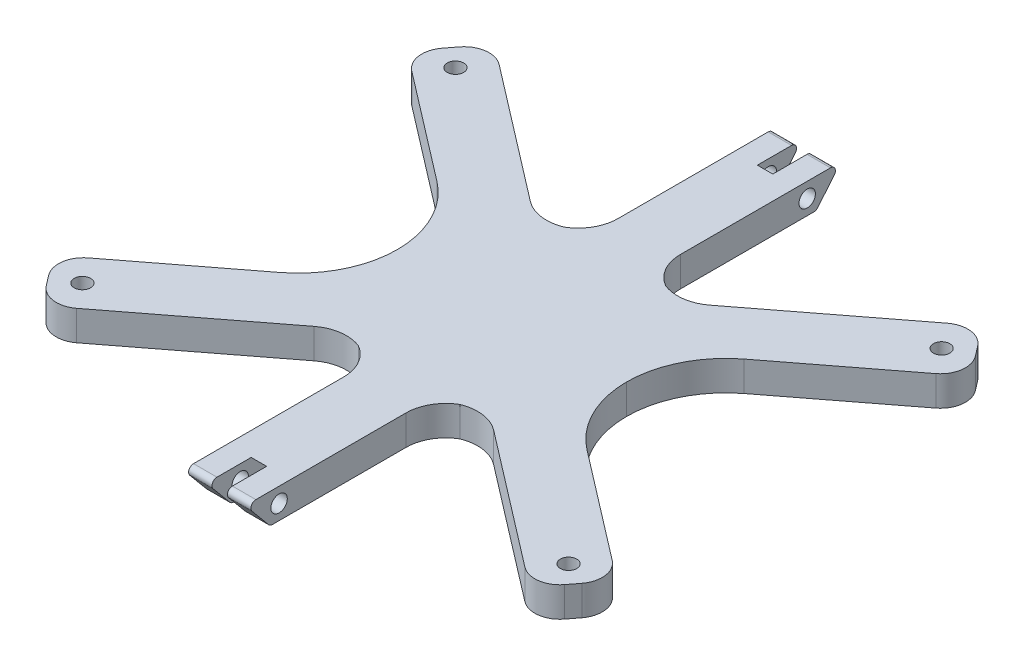
SolidWorks part; units mm, degrees
ref_plane "Front Plane" through (0, 0, 0) normal (0, 0, 1) x (1, 0, 0)
ref_plane "Top Plane" through (0, 0, 0) normal (0, 1, 0) x (1, 0, 0)
ref_plane "Right Plane" through (0, 0, 0) normal (1, 0, 0) x (0, 0, -1)
sketch "Sketch1" plane through (0, 0, 0) normal (0, 1, 0) x (1, 0, 0)
  circle A0 centre (0, 0) radius 23
  dimension "D1" = 46
extrude "Boss-Extrude1" add sketch "Sketch1" along normal mid plane 6
sketch "Sketch2" plane through (0, 0, 0) normal (0, 1, 0) x (1, 0, 0)
  line L0 (-21.3653, 8.5162) -> (-56.5628, 35.5242)
  line L1 (0.2695, -0.2068) -> (-63.7589, 48.924) construction
  line L2 (-48.9532, 45.4411) -> (-13.7557, 18.4331)
  line L3 (0, 37.6664) -> (0, -25.0328) construction
  line L4 (-48.9532, 45.4411) -> (-56.5628, 35.5242)
  circle A0 centre (0, 0) radius 23 construction
  arc A1 (-13.7557, 18.4331) -> (-21.3653, 8.5162) centre (0, 0) ccw
  point P9 (-52.758, 40.4826)
  dimension "D1" = 66.5
  dimension "D2" = 52.5
  dimension "D3" = 12.5
extrude "Boss-Extrude2" add sketch "Sketch2" along normal up to surface and the other way up to surface up to face at (0, 3, 23) other way up to face at (0, -3, 23)
mirror "Mirror1" about plane through (0, 0, 0) normal (1, 0, 0) of "Boss-Extrude2"
mirror "Mirror2" about plane through (0, 0, 0) normal (0, 0, 1) of "Mirror1", "Boss-Extrude2"
sketch "Sketch4" plane through (0, 3, 0) normal (0, 1, 0) x (1, 0, 0)
  line L0 (0, 65.599) -> (0, -44.8835) construction
  line L2 (-6.25, 59.8) -> (6.25, 59.8)
  line L4 (-6.25, 59.8) -> (-6.25, 22.1345)
  line L5 (6.25, 59.8) -> (6.25, 22.1345)
  arc A2 (13.7557, 18.4331) -> (-13.7557, 18.4331) centre (0, 0) ccw construction
  arc A3 (6.25, 22.1345) -> (-6.25, 22.1345) centre (0, 0) ccw
  point P8 (0, 59.8)
  dimension "D1" = 12.5
  dimension "D2" = 59.8
extrude "Boss-Extrude4" add sketch "Sketch4" against normal up to surface (6 mm away) up to face at (0, -3, 0)
mirror "Mirror6" about plane through (0, 0, 0) normal (0, 0, 1) of "Boss-Extrude4"
fillet "Fillet4" radius 8 8 edges at (-13.7557, 0, 18.4331) (-6.25, 0, 22.1345) (6.25, 0, 22.1345) (13.7557, 0, 18.4331) (13.7557, 0, -18.4331) (6.25, 0, -22.1345) (-6.25, 0, -22.1345) (-13.7557, 0, -18.4331)
fillet "Fillet5" radius 20 4 edges at (-21.3653, 0, 8.5162) (-21.3653, 0, -8.5162) (21.3653, 0, 8.5162) (21.3653, 0, -8.5162)
sketch "Sketch3" plane through (0, 3, 0) normal (0, 1, 0) x (1, 0, 0)
  circle A0 centre (-48.7912, 37.4388) radius 1.65
  dimension "D1" = 3.3
  dimension "D2" = 61.5
extrude "Cut-Extrude1" cut sketch "Sketch3" against normal through all
mirror "Mirror3" about plane through (0, 0, 0) normal (1, 0, 0) of "Cut-Extrude1"
mirror "Mirror4" about plane through (0, 0, 0) normal (0, 0, 1) of "Mirror3", "Cut-Extrude1"
sketch "Sketch13" plane through (-6.25, 0, 0) normal (-1, 0, 0) x (0, 0, 1)
  line L0 (-59.8, -3) -> (-59.8, 3) construction
  circle A0 centre (-53, 0) radius 1.65
  point P6 (-59.8, 0)
  dimension "D2" = 3.3
  dimension "D1" = 53
extrude "Cut-Extrude9" cut sketch "Sketch13" against normal blind 14
sketch "Sketch12" plane through (-6.25, 0, 0) normal (-1, 0, 0) x (0, 0, 1)
  line L0 (-59.8, 3) -> (-54.8, -3)
  line L2 (-54.8, -3) -> (-59.8, -3)
  line L3 (-59.8, -3) -> (-59.8, 3)
  line L4 (-27.5307, -3) -> (-59.8, -3) construction
  dimension "D1" = 5
extrude "Cut-Extrude8" cut sketch "Sketch12" against normal up to surface (12.5 mm away) up to face at (6.25, 0, -54.65)
sketch "Sketch14" plane through (0, 3, 0) normal (0, 1, 0) x (1, 0, 0)
  line L0 (-1.55, 59.8) -> (1.55, 59.8)
  line L1 (6.25, 59.8) -> (-6.25, 59.8) construction
  line L2 (1.55, 59.8) -> (1.55, 50.8)
  line L3 (1.55, 50.8) -> (-1.55, 50.8)
  line L4 (-1.55, 50.8) -> (-1.55, 59.8)
  point P4 (0, 50.8)
  dimension "D1" = 9
  dimension "D2" = 3.1
extrude "Cut-Extrude10" cut sketch "Sketch14" against normal blind 14
sketch "Sketch15" plane through (-1.55, 0, 0) normal (1, 0, 0) x (0, 0, -1)
  line L0 (50.8, 3) -> (40.4826, -3)
  line L1 (45.4411, -3) -> (35.5242, -3) construction
  line L2 (40.4826, -3) -> (50.8, -3)
  line L3 (50.8, -3) -> (50.8, 3)
extrude "Cut-Extrude11" cut sketch "Sketch15" along normal up to surface (3.1 mm away) up to face at (1.55, 0, -54.05)
mirror "Mirror8" about plane through (0, 0, 0) normal (0, 0, 1) of "Cut-Extrude11", "Cut-Extrude8", "Cut-Extrude9", "Cut-Extrude10"
fillet "Fillet3" radius 5 8 edges at (48.9532, 0, 45.4411) (56.5628, 0, 35.5242) (56.5628, 0, -35.5242) (48.9532, 0, -45.4411) (-48.9532, 0, -45.4411) (-56.5628, 0, -35.5242) (-56.5628, 0, 35.5242) (-48.9532, 0, 45.4411)
fillet "Fillet7" radius 1 8 edges at (3.9, -3, 54.8) (-3.9, -3, 54.8) (3.9, 3, 59.8) (-3.9, 3, 59.8) (-3.9, -3, -54.8) (3.9, -3, -54.8) (3.9, 3, -59.8) (-3.9, 3, -59.8)
